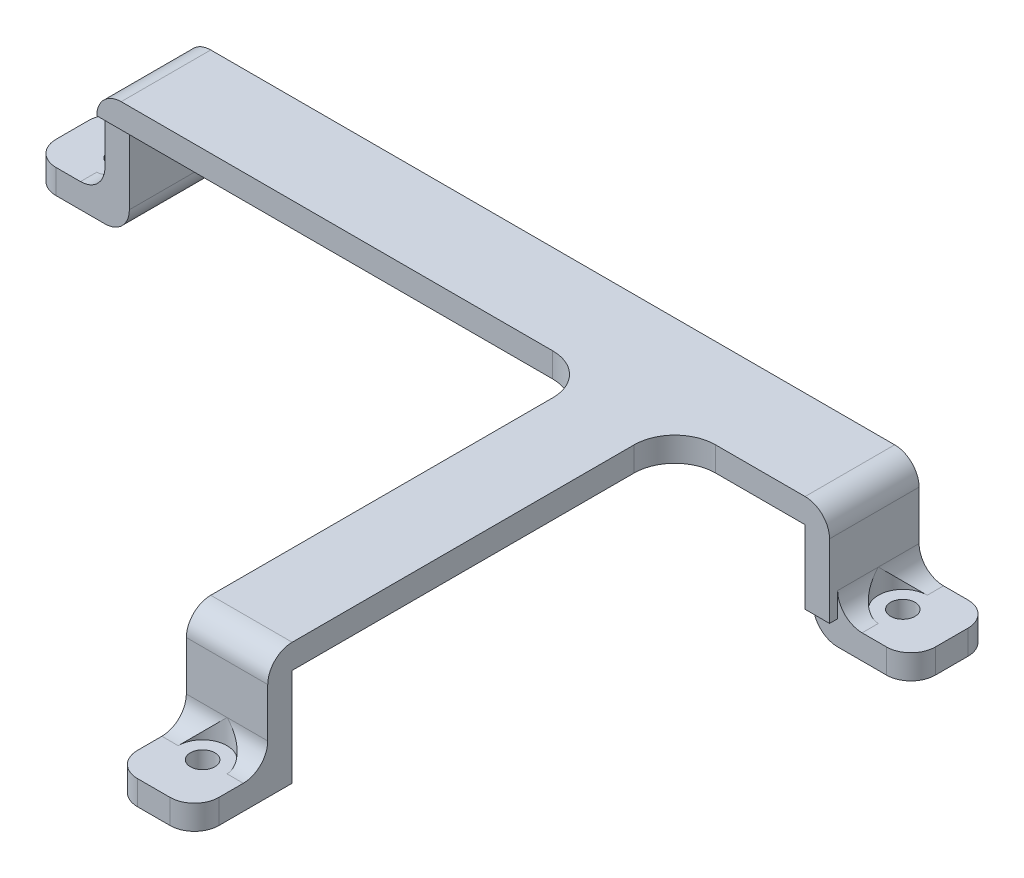
SolidWorks part; units mm, degrees
ref_plane "Front Plane" through (0, 0, 0) normal (0, 0, 1) x (1, 0, 0)
ref_plane "Top Plane" through (0, 0, 0) normal (0, 1, 0) x (1, 0, 0)
ref_plane "Right Plane" through (0, 0, 0) normal (1, 0, 0) x (0, 0, -1)
sketch "Sketch1" plane through (0, 0, 0) normal (0, 1, 0) x (1, 0, 0)
  line L1 (-75, 64) -> (-63, 64)
  line L2 (-75, 64) -> (-75, 54)
  line L3 (-75, 54) -> (-63, 54)
  line L4 (-63, 64) -> (-63, 54)
  line L5 (21, 64) -> (33, 64)
  line L6 (21, 64) -> (21, 54)
  line L7 (21, 54) -> (33, 54)
  line L8 (33, 64) -> (33, 54)
  line L9 (-5, 6) -> (5, 6)
  line L10 (-5, 6) -> (-5, -6)
  line L11 (-5, -6) -> (5, -6)
  line L12 (5, 6) -> (5, -6)
  circle A0 centre (0, 0) radius 1.5
  circle A1 centre (-69, 59) radius 1.5
  circle A2 centre (27, 59) radius 1.5
  point P19 (-75, 59)
  point P21 (33, 59)
  point P22 (0, 6)
  dimension "D1" = 3
  dimension "D3" = 59
  dimension "D2" = 69
  dimension "D4" = 96
  dimension "D5" = 6
  dimension "D6" = 6
  dimension "D7" = 12
  dimension "D8" = 12
  dimension "D9" = 6
  dimension "D10" = 12
  dimension "D11" = 10
  dimension "D12" = 10
  dimension "D13" = 10
extrude "Screw tabs" add sketch "Sketch1" along normal blind 3
sketch "Sketch2" plane through (0, 3, 0) normal (0, 1, 0) x (1, 0, 0)
  line L0 (-75, 54) -> (-63, 54) construction
  line L1 (-63, 64) -> (-66, 64)
  line L2 (-63, 64) -> (-63, 54)
  line L3 (-63, 54) -> (-66, 54)
  line L4 (-66, 64) -> (-66, 54)
  line L5 (5, -6) -> (5, 6) construction
  line L6 (21, 64) -> (24, 64)
  line L7 (21, 64) -> (21, 53)
  line L8 (21, 53) -> (24, 53)
  line L9 (24, 64) -> (24, 53)
  line L10 (-5, 6) -> (5, 6)
  line L11 (-5, 6) -> (-5, 3)
  line L12 (-5, 3) -> (5, 3)
  line L13 (5, 6) -> (5, 3)
  dimension "D1" = 3
extrude "Vertical extrude" add sketch "Sketch2" along normal blind 9
sketch "Sketch3" plane through (0, 12, 0) normal (0, 1, 0) x (1, 0, 0)
  line L0 (5, 3) -> (5, 6) construction
  line L1 (-66, 64) -> (24, 64)
  line L2 (-66, 64) -> (-66, 53)
  line L3 (-66, 53) -> (-10, 53)
  line L4 (24, 64) -> (24, 53)
  line L5 (-5, 3) -> (5, 3)
  line L6 (-5, 3) -> (-5, 48)
  line L8 (5, 3) -> (5, 48)
  line L9 (10, 53) -> (24, 53)
  arc A0 (10, 53) -> (5, 48) centre (10, 48) ccw
  arc A1 (-5, 48) -> (-10, 53) centre (-10, 48) ccw
  point P15 (5, 53)
  point P18 (0, 0)
  point P19 (24, 53)
  dimension "D1" = 5
extrude "Top bracket" add sketch "Sketch3" along normal blind 3
fillet "3mm edge rounding" radius 3 14 edges at (-63, 0, -59) (21, 0, -59) (24, 3, -59) (0, 3, -3) (-66, 3, -59) (33, 1.5, -64) (33, 1.5, -54) (5, 1.5, 6) (-5, 1.5, 6) (-75, 1.5, -64) (-75, 1.5, -54) (24, 15, -58.5) (0, 15, -3) (-66, 15, -58.5)
sketch "Sketch4" plane through (0, 3, 0) normal (0, 1, 0) x (1, 0, 0)
  circle A8 centre (-69, 59) radius 3
  circle A9 centre (-69, 59) radius 3
  circle A11 centre (0, 0) radius 3
  circle A12 centre (0, 0) radius 3
  circle A14 centre (27, 59) radius 3
  circle A15 centre (27, 59) radius 3
  dimension "D1" = 1.5
  dimension "D2" = 1.5
  dimension "D3" = 1.5
extrude "Screwhole clearup" cut sketch "Sketch4" along normal through all
